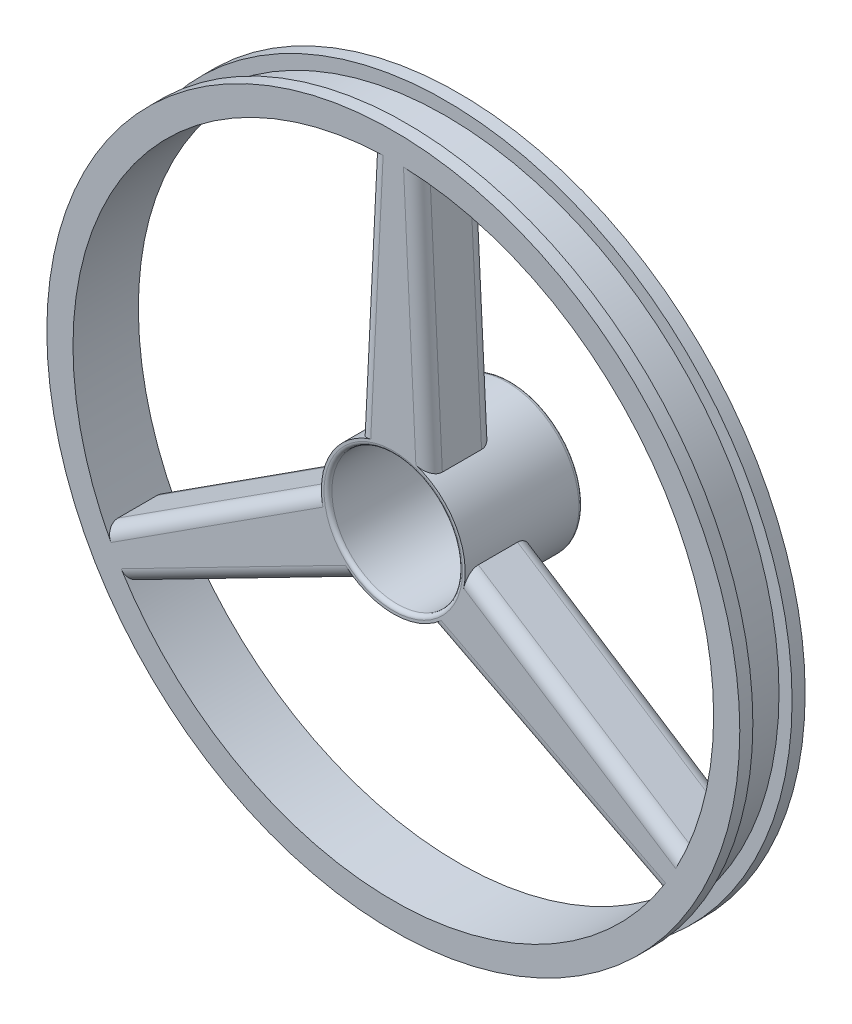
SolidWorks part; units mm, degrees
ref_plane "前视基准面" through (0, 0, 0) normal (0, 0, 1) x (1, 0, 0)
ref_plane "上视基准面" through (0, 0, 0) normal (0, 1, 0) x (1, 0, 0)
ref_plane "右视基准面" through (0, 0, 0) normal (1, 0, 0) x (0, 0, -1)
sketch "草图1" plane through (0, 0, 0) normal (0, 0, 1) x (1, 0, 0)
  circle A0 centre (0, 0) radius 265
  circle A1 centre (0, 0) radius 245
  dimension "D1" = 490
  dimension "D2" = 530
extrude "凸台-拉伸1" add sketch "草图1" along normal blind 50
sketch "草图2" plane through (0, 0, 0) normal (0, 0, 1) x (1, 0, 0)
  circle A0 centre (0, 0) radius 55
  circle A2 centre (0, 0) radius 50
  dimension "D1" = 110
  dimension "D3" = 100
extrude "凸台-拉伸2" add sketch "草图2" along normal blind 50 separate body
sketch "草图3" plane through (0, 0, 0) normal (0, 0, 1) x (1, 0, 0)
  line L0 (-55, 0) -> (-220.528, -106.7351)
  line L1 (47.6314, -27.5) -> (211.9575, -122.3737) construction
  line L2 (47.6314, -27.5) -> (229.4967, -132.5) construction
  line L3 (-47.6314, -27.5) -> (-210.2204, -121.3708) construction
  line L4 (0, 55) -> (0, 244.3916) construction
  line L5 (-27.5, -47.6314) -> (-202.6993, -137.6153)
  line L6 (-27.5, 47.6314) -> (-17.8287, 244.3504)
  line L7 (27.5, 47.6314) -> (17.8287, 244.3504)
  line L8 (55, 0) -> (220.528, -106.7351)
  line L9 (27.5, -47.6314) -> (202.6993, -137.6153)
  circle A0 centre (0, 0) radius 245 construction
  circle A1 centre (0, 0) radius 55 construction
  circle A2 centre (0, 0) radius 55
  circle A3 centre (0, 0) radius 245
  point P26 (0, 0)
  dimension "D1" = 3
extrude "凸台-拉伸3" add sketch "草图3" along normal blind 50 contours L0 A3 L5 A2 | L9 A3 L8 A2 | L7 A3 L6 A2 region at (-122.9597, -70.9908, 0) region at (0, 141.9817, 0) region at (122.9597, -70.9908, 0)
fillet "圆角1" radius 10 10 edges at (137.764, -53.3676, 0) (-22.6643, 145.9909, 50) (22.6643, 145.9909, 50) (22.6643, 145.9909, 0) (-115.0997, -92.6234, 0) (-137.764, -53.3676, 0) (-137.764, -53.3676, 50) (-115.0997, -92.6234, 50) (115.0997, -92.6234, 50) (137.764, -53.3676, 50)
sketch "草图4" plane through (0, 0, 0) normal (0, 1, 0) x (1, 0, 0)
  line L0 (0, 50.8028) -> (0, -79.9691) construction
  line L1 (-304.2205, -25) -> (300.5995, -25) construction
  line L2 (-265, -40) -> (-265, -10)
  line L3 (-265, 0) -> (-265, -50) construction
  line L4 (-265, -10) -> (-255, -10)
  line L5 (-255, -10) -> (-255, -40)
  line L6 (-265, -40) -> (-255, -40)
  point P11 (-265, -25)
  point P13 (-255, -25)
  dimension "D1" = 15
  dimension "D2" = 10
revolve "切除-旋转1" cut sketch "草图4" angle 360 about L0
fillet "圆角2" radius 3 1 edges at (50, 0, 50)
sketch "草图6" plane through (0, 0, 0) normal (0, 0, 1) x (1, 0, 0)
  circle A0 centre (0, 0) radius 50
  circle A1 centre (0, 0) radius 55
extrude "凸台-拉伸4" add sketch "草图6" against normal blind 30
sketch "草图7" plane through (0, 0, -30) normal (0, 0, -1) x (-1, 0, 0)
  circle A0 centre (0, 0) radius 55
extrude "凸台-拉伸5" add sketch "草图7" along normal blind 10
fillet "圆角3" radius 3 1 edges at (-55, 0, -40)
sketch "草图8" plane through (0, 0, -30) normal (0, 0, 1) x (1, 0, 0)
  circle A0 centre (0, 0) radius 31
  dimension "D1" = 62
extrude "切除-拉伸1" cut sketch "草图8" against normal blind 10
